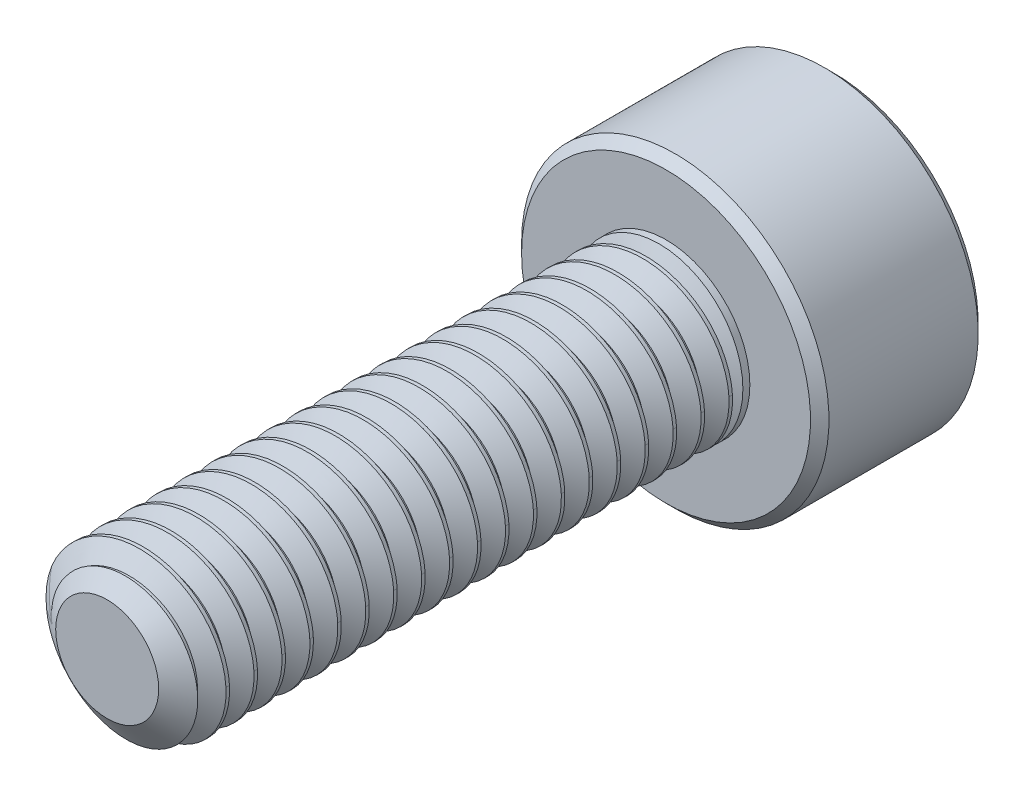
SolidWorks part; units mm, degrees
ref_plane "Front Plane" through (0, 0, 0) normal (0, 0, 1) x (1, 0, 0)
ref_plane "Top Plane" through (0, 0, 0) normal (0, 1, 0) x (1, 0, 0)
ref_plane "Right Plane" through (0, 0, 0) normal (1, 0, 0) x (0, 0, -1)
sketch "Sketch1" plane through (0, 0, 0) normal (0, 0, 1) x (1, 0, 0)
  circle A0 centre (0, 0) radius 1.5
  dimension "OD" = 3
extrude "Extrude1" add sketch "Sketch1" against normal blind 10
sketch "Sketch2" plane through (0, 0, 0) normal (0, 0, 1) x (1, 0, 0)
  circle A0 centre (0, 0) radius 1.5 construction
  circle A1 centre (0, 0) radius 1.5
curve "Helix/Spiral1" pitch 0.5 height 10.5 radius 1.5 centre (0, 0, 0) axis (0, 0, -1) start towards (0, 1, 0) parameters "pitch"=0.5
sketch "Sketch3" plane through (0, 0, 0) normal (1, 0, 0) x (0, 0, -1)
  line L0 (-0.4375, 1.5) -> (-0.25, 1.1752)
  line L1 (-0.25, 1.1752) -> (-0.1875, 1.1752)
  line L2 (-0.1875, 1.1752) -> (0, 1.5)
  line L3 (-0.4375, 1.5) -> (0, 1.5)
  line L4 (-0.2187, 1.5) -> (-0.2187, 1.1752) construction
  line L5 (-0.3437, 1.3376) -> (-0.0937, 1.3376) construction
  line L6 (0, 1.5) -> (0, -1.5) construction
  line L7 (0, -1.5) -> (10, -1.5) construction
  point P11 (2.25, -1.5)
  dimension "D1" = 0.0625
  dimension "D2" = 0.25
  dimension "D3" = 60
  dimension "D4" = 2.25
sweep "Cut-Sweep1" cut profiles "Sketch3" path "Helix/Spiral1" align with end faces yes
sketch "Sketch4" plane through (0, 0, 0) normal (1, 0, 0) x (0, 0, -1)
  line L0 (0.4053, 1.5) -> (0, 0.9212)
  line L1 (0, 0.9212) -> (0, 1.5)
  line L2 (0.4053, 1.5) -> (0, 1.5)
  line L3 (-0.4375, 1.5) -> (0, 1.5) construction
  line L4 (0, 0) -> (7.0209, 0) construction
  dimension "D1" = 55
  dimension "D2" = 0.254
revolve "Cut-Revolve1" cut sketch "Sketch4" angle 360 about L4
sketch "Sketch5" plane through (0, 0, 0) normal (1, 0, 0) x (0, 0, -1)
  line L0 (10, -1.1822) -> (10, 1.0703) construction
  line L1 (10, 1.5) -> (0.1203, 1.5)
  line L2 (10, 1.5) -> (10, 0)
  line L3 (10, 0) -> (0.0001, 0)
  line L4 (0.0001, 1.1698) -> (0.0001, 0)
  line L5 (0.1203, 1.5) -> (0.0001, 1.1698)
  line L6 (0, 0) -> (9.9695, 0) construction
  point P3 (0.0001, 1.5)
  point P10 (0.0001, 1.5)
  dimension "D1" = 0.3302
  dimension "Thread min" = 0.0001
  dimension "D3" = 20
revolve "partially thread" [suppressed] add sketch "Sketch5" angle 360 about L6
sketch "Sketch6" plane through (0, 0, -10) normal (0, 0, -1) x (-1, 0, 0)
  circle A0 centre (0, 0) radius 2.75
  dimension "head dia" = 5.5
extrude "Extrude2" add sketch "Sketch6" along normal blind 3
sketch "Sketch7" plane through (0, 0, -13) normal (0, 0, -1) x (-1, 0, 0)
  line L1 (0, 1.4434) -> (-1.25, 0.7217)
  line L2 (-1.25, 0.7217) -> (-1.25, -0.7217)
  line L3 (-1.25, -0.7217) -> (0, -1.4434)
  line L4 (0, -1.4434) -> (1.25, -0.7217)
  line L5 (1.25, -0.7217) -> (1.25, 0.7217)
  line L6 (1.25, 0.7217) -> (0, 1.4434)
  circle A0 centre (0, 0) radius 1.25 construction
  dimension "hex dia" = 2.5
extrude "Cut-Extrude1" cut sketch "Sketch7" against normal blind 1.875
sketch "Sketch8" plane through (0, 0, -13) normal (0, 0, -1) x (-1, 0, 0)
  circle A0 centre (0, 0) radius 1.4434
extrude "Cut-Extrude2" cut sketch "Sketch8" against normal through all draft 45
chamfer "Chamfer1" distance 0.165 angle 45 2 edges at (-2.75, 0, -13) (-2.75, 0, -10)
sketch "Sketch9" plane through (0, 0, 0) normal (1, 0, 0) x (0, 0, -1)
  line L0 (0, 1.5) -> (0, -1.5) construction
  line L1 (2.75, 1.5) -> (2.75, -1.5) construction
  dimension "D1" = 2.75
sketch "Sketch10" plane through (0, 0, 0) normal (1, 0, 0) x (0, 0, -1)
  line L0 (10, 1.5) -> (10, 0)
  line L1 (10, 1.5) -> (9.875, 1.5)
  line L2 (9.875, 1.5) -> (9.2537, 0)
  line L3 (10, 0) -> (9.2537, 0)
  line L4 (10, 2.585) -> (10, -2.585) construction
  dimension "D1" = 22.5
  dimension "D2" = 0.125
revolve "Revolve1" add sketch "Sketch10" angle 360 about L3
equation "\"D3@Helix/Spiral1\" = \"screw length@Extrude1\"+\"pitch@Helix/Spiral1\""
equation "\"D1@Sketch3\" = \"pitch@Helix/Spiral1\"*.125"
equation "\"D2@Sketch3\" = \"pitch@Helix/Spiral1\"*.5"
equation "\"D1@Cut-Extrude1\" = \"hex dia@Sketch7\"*.75"
equation "\"D1@Chamfer1\" = \"head dia@Sketch6\"*.03"
equation "\"D1@Sketch9\" = \"pitch@Helix/Spiral1\"*5.5"
equation "\"D2@Sketch10\" = \"pitch@Helix/Spiral1\"*.25"
equation "\"D4@Sketch3\" = \"pitch@Helix/Spiral1\"*4.50"
